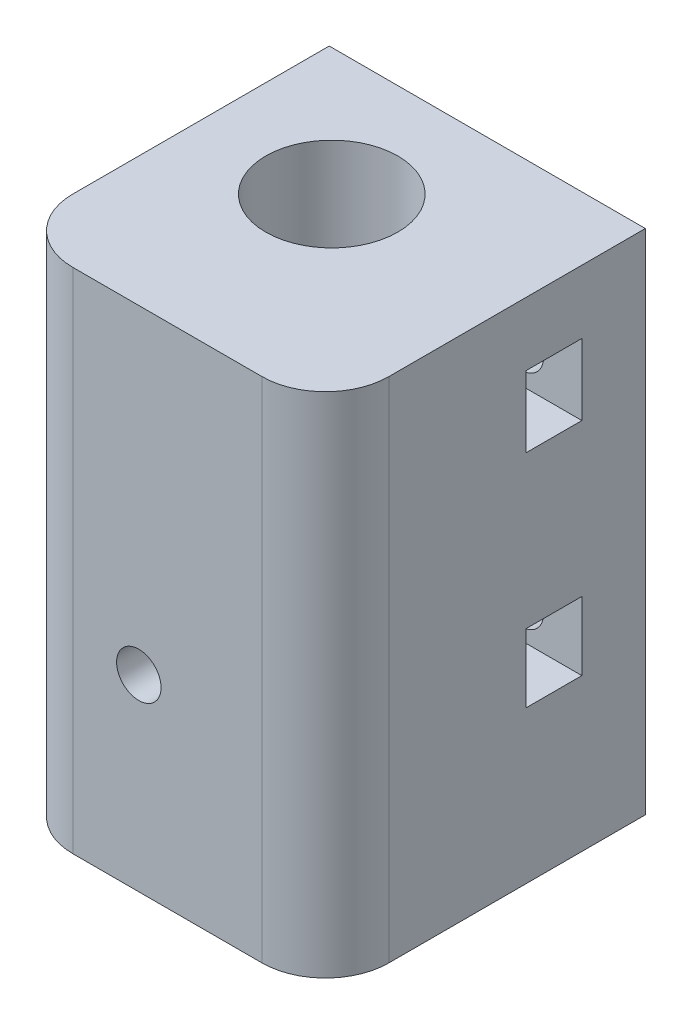
SolidWorks part; units mm, degrees
material "20% infill ABS"
ref_plane "Front" through (0, 0, 0) normal (0, 0, 1) x (1, 0, 0)
ref_plane "Top" through (0, 0, 0) normal (0, 1, 0) x (1, 0, 0)
ref_plane "Right" through (0, 0, 0) normal (1, 0, 0) x (0, 0, -1)
sketch "Sketch1" plane through (0, 0, 0) normal (0, 1, 0) x (1, 0, 0)
  line L1 (0, 0) -> (-24.9, 0)
  line L7 (-24.9, -32.2) -> (0, -32.2)
  line L8 (0, -32.2) -> (0, 0)
  line L11 (-24.9, 0) -> (-24.9, -32.2)
  line L12 (-24.9, -17.95) -> (-18.9, -17.95) construction
  line L13 (-18.9, -17.95) -> (-18.9, -16.7) construction
  line L14 (-18.9, -16.7) -> (-14.9, -16.7) construction
  line L15 (-14.9, -16.7) -> (-14.9, -22.2) construction
  line L16 (-14.9, -22.2) -> (-18.9, -22.2) construction
  line L17 (-18.9, -22.2) -> (-18.9, -20.95) construction
  line L18 (-18.9, -20.95) -> (-24.9, -20.95) construction
  line L19 (-6.25, 0) -> (-6.25, -6) construction
  line L20 (-6.25, -6) -> (-7.5, -6) construction
  line L21 (-7.5, -6) -> (-7.5, -10) construction
  line L22 (-7.5, -10) -> (-2, -10) construction
  line L23 (-2, -10) -> (-2, -6) construction
  line L24 (-2, -6) -> (-3.25, -6) construction
  line L25 (-3.25, -6) -> (-3.25, 0) construction
  circle A0 centre (-14.7, -10) radius 5.2 construction
  dimension "D2" = 10.4
  dimension "D7" = 5
  dimension "D1" = 5.5
  dimension "D3" = 10
  dimension "D4" = 3
  dimension "D5" = 4
  dimension "D6" = 10
  dimension "D8" = 2
  dimension "D9" = 2
  dimension "D10" = 10
  dimension "D11" = 3
extrude "Boss-Extrude1" add sketch "Sketch1" along normal blind 40
sketch "Sketch3" plane through (0, 0, 0) normal (0, -1, 0) x (1, 0, 0)
  circle A0 centre (-14.7, 10) radius 5.2 construction
  circle A1 centre (-14.7, 10) radius 5.2
extrude "Cut-Extrude2" cut sketch "Sketch3" against normal blind 20
ref_plane "Plane1" through (0, 25, 0) normal (0, -1, 0) x (-1, 0, 0)
sketch "Sketch4" plane through (0, 25, 0) normal (0, -1, 0) x (-1, 0, 0)
  circle A1 centre (14.7, -10) radius 5.2
  circle A2 centre (14.7, -10) radius 5.2
  dimension "D1" = 0
extrude "Cut-Extrude3" cut sketch "Sketch4" against normal blind 20
sketch "Sketch5" plane through (-24.9, 0, 0) normal (-1, 0, 0) x (0, 0, 1)
  line L0 (-1.488, -9.9) -> (56.6705, -8.9029)
  line L1 (56.6705, -8.9029) -> (55.2731, 72.6)
  line L2 (55.2731, 72.6) -> (22.512, 72.6)
  arc A0 (-1.488, -9.9) -> (22.512, 72.6) centre (-131.2848, 72.6) ccw construction
  arc A1 (-1.488, -9.9) -> (22.512, 72.6) centre (-131.2848, 72.6) ccw
extrude "Cut-Extrude4" [suppressed] cut sketch "Sketch5" against normal blind 30
sketch "Sketch6" plane through (0, 25, 0) normal (0, 1, 0) x (1, 0, 0)
  circle A0 centre (-14.7, -10) radius 5.2 construction
  circle A1 centre (-14.7, -10) radius 5.2
  circle A2 centre (-14.7, -10) radius 7.7
  dimension "D1" = 2.5
extrude "Boss-Extrude2" add sketch "Sketch6" against normal up to surface (25 mm away) up to face at (-14.7, 0, 4.8)
fillet "Fillet1" [suppressed] radius 10
ref_plane "Plane2" through (0, 0, 5) normal (0, 0, -1) x (-1, 0, 0)
sketch "Sketch7" plane through (0, 0, 5) normal (0, 0, -1) x (-1, 0, 0)
  line L0 (19.9, 40) -> (9.5, 40) construction
  line L1 (19.9, 40) -> (9.5, 40)
  line L2 (0, 40) -> (24.9, 40) construction
  line L4 (3.2087, 29.4) -> (6.3834, 29.4)
  line L5 (6.3834, 29.4) -> (8, 32.2)
  line L6 (8, 32.2) -> (6.3834, 35)
  line L7 (6.3834, 35) -> (3.2691, 35)
  line L10 (3.151, 12) -> (6.3257, 12)
  line L11 (6.3257, 12) -> (7.8845, 14.7)
  line L12 (7.8845, 14.7) -> (6.3257, 17.4)
  line L13 (6.3257, 17.4) -> (3.0955, 17.4)
  line L15 (0, 40) -> (0, 0) construction
  line L16 (3.2691, 35) -> (0, 35)
  line L17 (0, 35) -> (0, 29.4)
  line L18 (0, 29.4) -> (3.2087, 29.4)
  line L19 (3.0955, 17.4) -> (0, 17.4)
  line L20 (0, 17.4) -> (0, 12)
  line L21 (0, 12) -> (3.151, 12)
  line L23 (3.2642, 17.4974) -> (1.6765, 14.7474) [skipped]
  line L24 (1.5929, 14.7974) -> (3.1806, 12.0474) [skipped]
  line L25 (3.1488, 34.9975) -> (1.5611, 32.2475) [skipped]
  line L26 (1.5178, 32.2275) -> (3.1055, 29.4775) [skipped]
  circle A0 centre (4.7668, 32.2) radius 2.75 construction
  circle A1 centre (4.7668, 14.7) radius 2.75 construction
  dimension "D1" = 5.6
  dimension "D2" = 5
  dimension "D3" = 12
  dimension "D4" = 8
extrude "Cut-Extrude5" cut sketch "Sketch7" against normal blind 4.4 contours L17 L18 L4 L5 L6 L7 L16 | L20 L21 L10 L11 L12 L13 L19 region at (-3.611, 32.2, 5) region at (-3.5668, 14.7, 5)
sketch "Sketch9" plane through (0, 0, 0) normal (0, 0, -1) x (-1, 0, 0)
  circle A0 centre (4.7668, 32.2) radius 1.75
  circle A1 centre (4.7668, 14.7) radius 1.75
  dimension "D1" = 3.5
extrude "Cut-Extrude6" cut sketch "Sketch9" against normal blind 13
fillet "Fillet2" [suppressed] radius 7
sketch "Sketch10" plane through (0, 0, 0) normal (1, 0, 0) x (0, 0, -1)
  line L0 (-25.2, 49.6804) -> (-25.2, -5.9425)
  line L1 (-25.2, -5.9425) -> (-34.662, -3.3055)
  line L2 (-34.662, -3.3055) -> (-53.0295, 40.7978)
  line L3 (-53.0295, 40.7978) -> (-25.2, 49.6804)
  line L4 (-4.8, 40) -> (-15.2, 40) construction
  line L5 (-4.8, 40) -> (-15.2, 40)
  line M9 (-32.2, 0) -> (0, 0)
  line M11 (0, 40) -> (-32.2, 40)
  line M12 (-32.2, 40) -> (-32.2, 0)
  dimension "D1" = 10
extrude "Cut-Extrude8" cut sketch "Sketch10" against normal blind 40 contours L3 L2 L1 L0 M9 M12 M11 | L0 M11 M12 M9 region at (0, 26.7524, 37.7181) region at (0, 20, 28.7)
fillet "Fillet3" radius 5 2 edges at (-24.9, 20, 25.2) (0, 20, 25.2)
ref_plane "Plane3" through (-19.9, 40, 25.2) normal (0, -1, 0) x (-1, 0, 0)
sketch "Sketch12" plane through (0, 0, 25.2) normal (0, 0, 1) x (1, 0, 0)
  line L0 (-19.9, 20) -> (-9.5, 20) construction
  line L1 (-19.9, 20) -> (-9.5, 20)
  line L2 (-14.7, 20) -> (-14.7, 14.8) construction
  circle A0 centre (-14.7, 14.8) radius 1.75
  dimension "D1" = 3.5
  dimension "D2" = 5.2
extrude "Cut-Extrude9" cut sketch "Sketch12" against normal through all contours A0 | A0 region at (-14.7, 14.8, 25.2)
